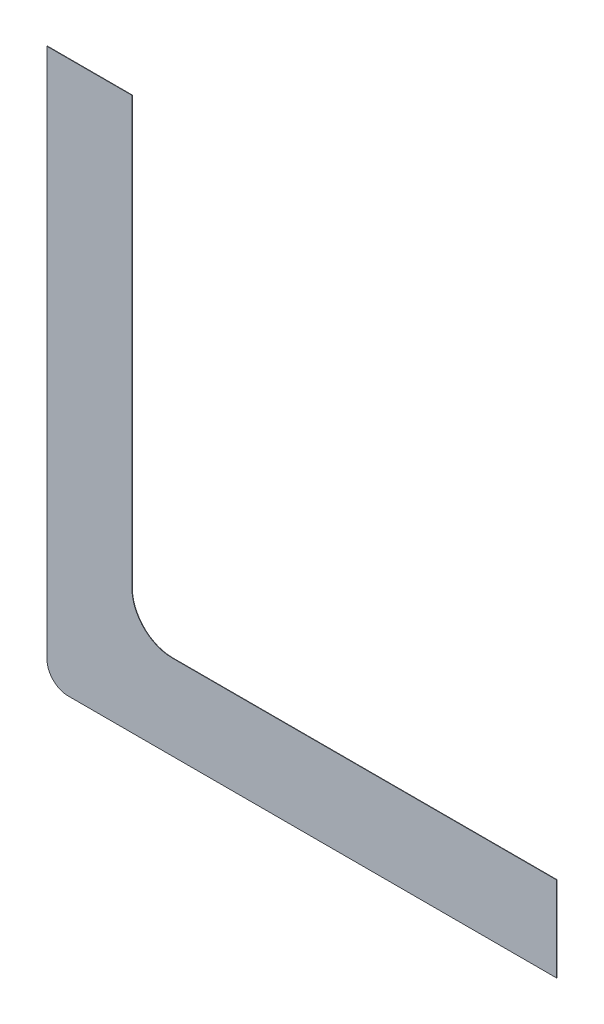
SolidWorks part; units mm, degrees
ref_plane "前视基准面" through (0, 0, 0) normal (0, 0, 1) x (1, 0, 0)
ref_plane "上视基准面" through (0, 0, 0) normal (0, 1, 0) x (1, 0, 0)
ref_plane "右视基准面" through (0, 0, 0) normal (1, 0, 0) x (0, 0, -1)
sketch "草图1" plane through (0, 0, 0) normal (0, 0, 1) x (1, 0, 0)
  line L0 (0, 0) -> (-120, 0)
  line L1 (-120, 0) -> (-120, 130)
  line L2 (-120, 130) -> (-100, 130)
  line L3 (-100, 130) -> (-100, 20)
  line L4 (-100, 20) -> (0, 20)
  line L5 (0, 20) -> (0, 0)
  dimension "D1" = 130
  dimension "D2" = 120
  dimension "D3" = 20
  dimension "D4" = 20
extrude "凸台-拉伸1" add sketch "草图1" along normal blind 0.1
fillet "圆角1" radius 9.5 1 edges at (-100, 20, 0.05)
fillet "圆角2" radius 5 1 edges at (-120, 0, 0.05)
sketch3d "3D草图2"
  line L0 (-100, 29.5, 0.1) -> (-100, 130, 0.1) construction
  line L1 (0, 20, 0.1) -> (-90.5, 20, 0.1) construction
  point P0 (-100, 117, 0.1)
  point P1 (-100, 78.9323, 0.1)
  point P4 (-80, 20, 0.1)
  point P5 (-15, 20, 0.1)
sketch3d "3D草图1" [suppressed]
  line L0 (-11.5, 30, 0.5) -> (-11.5, 100, 0.5) construction
  arc A0 (-1.5, 20, 0.5) -> (-11.5, 30, 0.5) centre (-1.5, 30, 0.5) ccw construction
  point P0 (-1.5, 20, 0.5)
  point P1 (-8.5711, 22.9289, 0.5)
  point P3 (-11.5, 30, 0.5)
  point P7 (-1.5, 30, -9.5)
  point P8 (-11.5, 49.1552, 0.5)
  point P10 (-11.5, 87.2694, 0.5)
